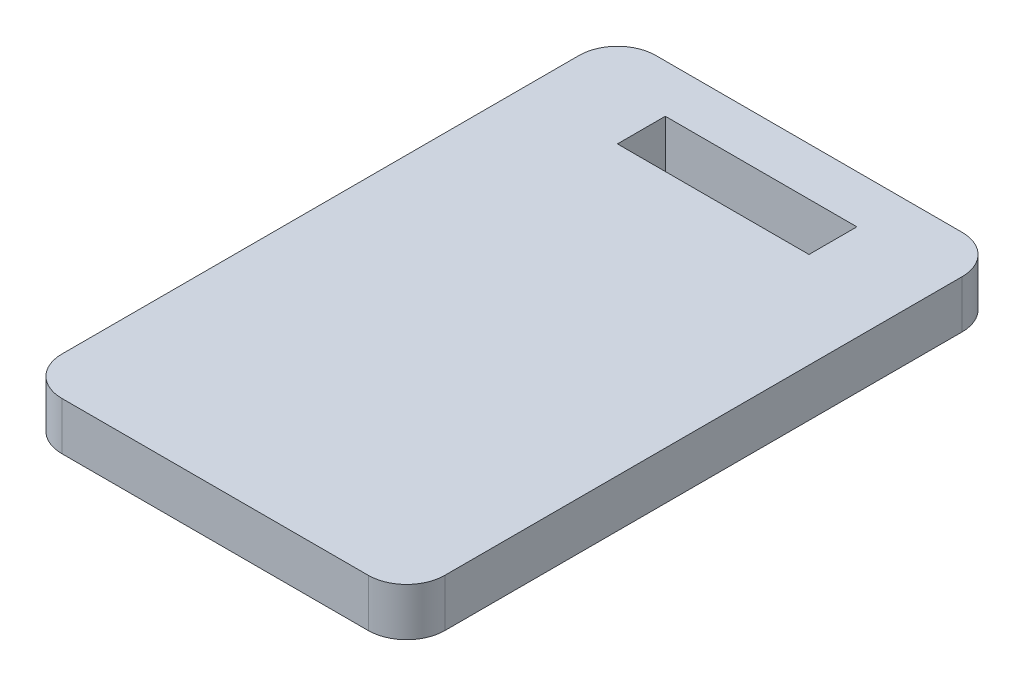
SolidWorks part; units mm, degrees
material "Acrylic (Medium-high impact)"
ref_plane "Front Plane" through (0, 0, 0) normal (0, 0, 1) x (1, 0, 0)
ref_plane "Top Plane" through (0, 0, 0) normal (0, 1, 0) x (1, 0, 0)
ref_plane "Right Plane" through (0, 0, 0) normal (1, 0, 0) x (0, 0, -1)
ref_plane "Plane1" through (0, 0, 0) normal (0, 1, 0) x (1, 0, 0)
sketch "Sketch1" plane through (0, 0, 0) normal (0, 1, 0) x (1, 0, 0)
  line L1 (0, 0) -> (25.4, 0)
  line L2 (0, 0) -> (0, 39.38)
  line L3 (0, 39.38) -> (25.4, 39.38)
  line L4 (25.4, 0) -> (25.4, 39.38)
  dimension "D1" = 39.38
  dimension "D2" = 25.4
extrude "Boss-Extrude1" add sketch "Sketch1" along normal blind 3.175
ref_plane "Plane2" through (0, 3.175, 0) normal (0, 1, 0) x (1, 0, 0)
sketch "Sketch2" plane through (0, 3.175, 0) normal (0, 1, 0) x (1, 0, 0)
  line L0 (0, 39.38) -> (0, 0) construction
  line L1 (6.35, 33.03) -> (19.05, 33.03)
  line L2 (6.35, 33.03) -> (6.35, 36.205)
  line L3 (6.35, 36.205) -> (19.05, 36.205)
  line L4 (19.05, 33.03) -> (19.05, 36.205)
  line L5 (25.4, 0) -> (25.4, 39.38) construction
  line L7 (25.4, 39.38) -> (0, 39.38) construction
  dimension "D1" = 6.35
  dimension "D2" = 6.35
  dimension "D3" = 3.175
  dimension "D4" = 3.175
extrude "Cut-Extrude1" cut sketch "Sketch2" against normal through all
fillet "Fillet1" radius 2.54 4 edges at (0, 1.5875, -39.38) (25.4, 1.5875, -39.38) (25.4, 1.5875, 0) (0, 1.5875, 0)
